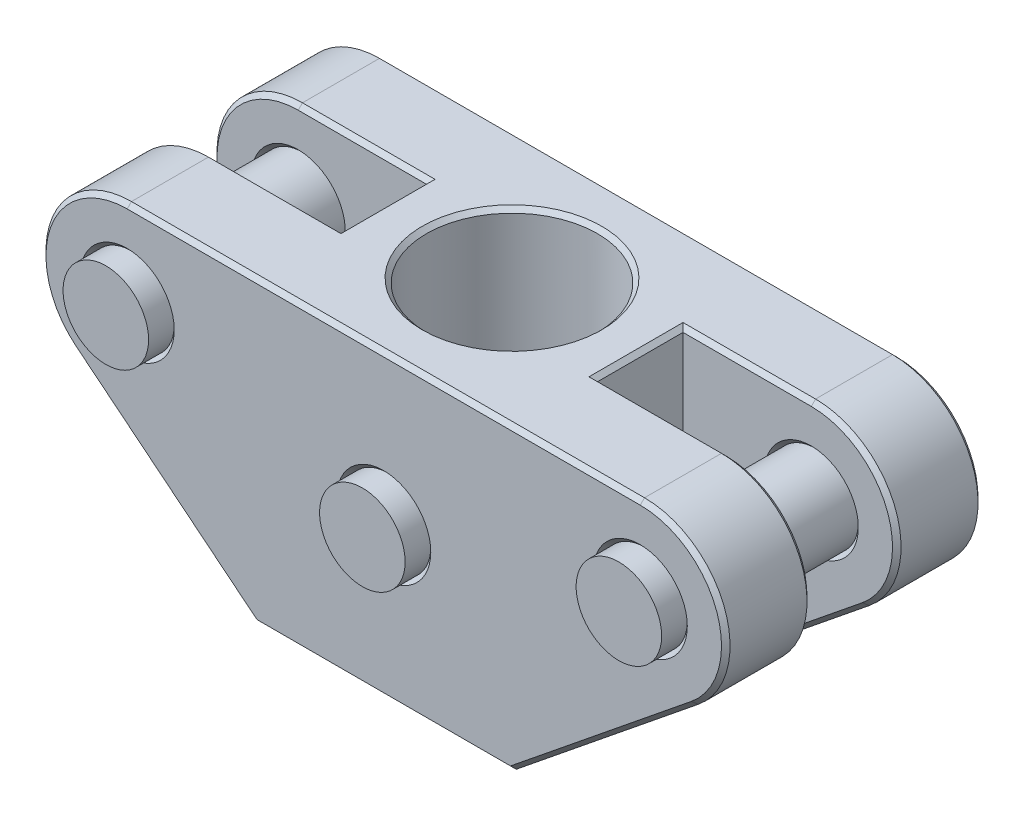
SolidWorks part; units mm, degrees
ref_plane "Front Plane" through (0, 0, 0) normal (0, 0, 1) x (1, 0, 0)
ref_plane "Top Plane" through (0, 0, 0) normal (0, 1, 0) x (1, 0, 0)
ref_plane "Right Plane" through (0, 0, 0) normal (1, 0, 0) x (0, 0, -1)
sketch "Sketch1" plane through (0, 0, 0) normal (0, 0, 1) x (1, 0, 0)
  line L0 (0, 0) -> (0, 7) construction
  line L1 (0, 0) -> (-3, 0)
  line L2 (-3, 0) -> (-7.258, 3.4452)
  line L3 (-6, 7) -> (0, 7)
  line L4 (0, 7) -> (0, 0)
  arc A0 (-7.258, 3.4452) -> (-6, 7) centre (-6, 5) cw
  circle A1 centre (-6, 5) radius 1
  arc A2 (0, 4.5) -> (0, 2.5) centre (0, 3.5) ccw
  dimension "D3" = 2
  dimension "D5" = 2
  dimension "D6" = 2
  dimension "D1" = 7
  dimension "D2" = 6
  dimension "D4" = 3
  dimension "D7" = 3.5
extrude "Boss-Extrude1" add sketch "Sketch1" along normal mid plane 6 contours A2 L4 L3 A0 L2 L1 A1 region at (-3.3081, 3.857, 0)
mirror "Mirror1" about plane through (0, 0, 0) normal (1, 0, 0) of "Boss-Extrude1"
sketch "Sketch2" plane through (0, 7, 0) normal (0, 1, 0) x (1, 0, 0)
  line L0 (-8, 3) -> (-8, -3) construction
  line L1 (-8, 1) -> (-3, 1)
  line L2 (-8, 1) -> (-8, -1)
  line L3 (-8, -1) -> (-3, -1)
  line L4 (-3, 1) -> (-3, -1)
  line L5 (-6, -3) -> (6, -3) construction
  line L6 (-6, 3) -> (6, 3) construction
  line L7 (0, 3) -> (0, -3) construction
  line L8 (3, 1) -> (3, -1)
  line L9 (8, -1) -> (3, -1)
  line L10 (8, 1) -> (8, -1)
  line L11 (8, 1) -> (3, 1)
  circle A0 centre (0, 0) radius 2
  dimension "D4" = 4
  dimension "D1" = 2
  dimension "D2" = 2
  dimension "D3" = 5
extrude "Cut-Extrude1" cut sketch "Sketch2" against normal through all both
chamfer "Chamfer1" distance 0.1 angle 45 37 edges at (-7, 5, -1) (5, 5, -1) (0, 0, 3) (0, 0, -3) (7, 5, 1) (5, 5, -3) (1, 3.5, -3) (-5, 5, -3) (-5, 5, 1) (1, 3.5, 3) (-5, 5, 3) (5, 5, 3) (0, 7, 2) (-5.129, 1.7226, -1) (-5.129, 1.7226, 1) (-7.8854, 5.6672, -1) (-7.8854, 5.6672, 1) (-4.5, 7, -1) (-3, 7, 0) (-4.5, 7, 1) (5.129, 1.7226, 1) (5.129, 1.7226, -1) (7.8854, 5.6672, 1) (7.8854, 5.6672, -1) (4.5, 7, 1) (4.5, 7, -1) (3, 7, 0) (-5.129, 1.7226, -3) (5.129, 1.7226, -3) (-7.8854, 5.6672, -3) (7.8854, 5.6672, -3) (0, 7, -3) (-5.129, 1.7226, 3) (5.129, 1.7226, 3) (-7.8854, 5.6672, 3) (7.8854, 5.6672, 3) (0, 7, 3)
sketch "Sketch3" plane through (0, 0, 3) normal (0, 0, 1) x (1, 0, 0)
  line L0 (0, 6.9) -> (0, 0.1) construction
  line L1 (6, 6.9) -> (-6, 6.9) construction
  line L2 (-2.9646, 0.1) -> (2.9646, 0.1) construction
  circle A0 centre (-6, 5) radius 1
  circle A1 centre (6, 5) radius 1
  circle A2 centre (0, 3.5) radius 1
  dimension "D1" = 2
  dimension "D2" = 2
extrude "Boss-Extrude2" add sketch "Sketch3" along normal blind 0.5 and the other way blind 6.5 separate body
